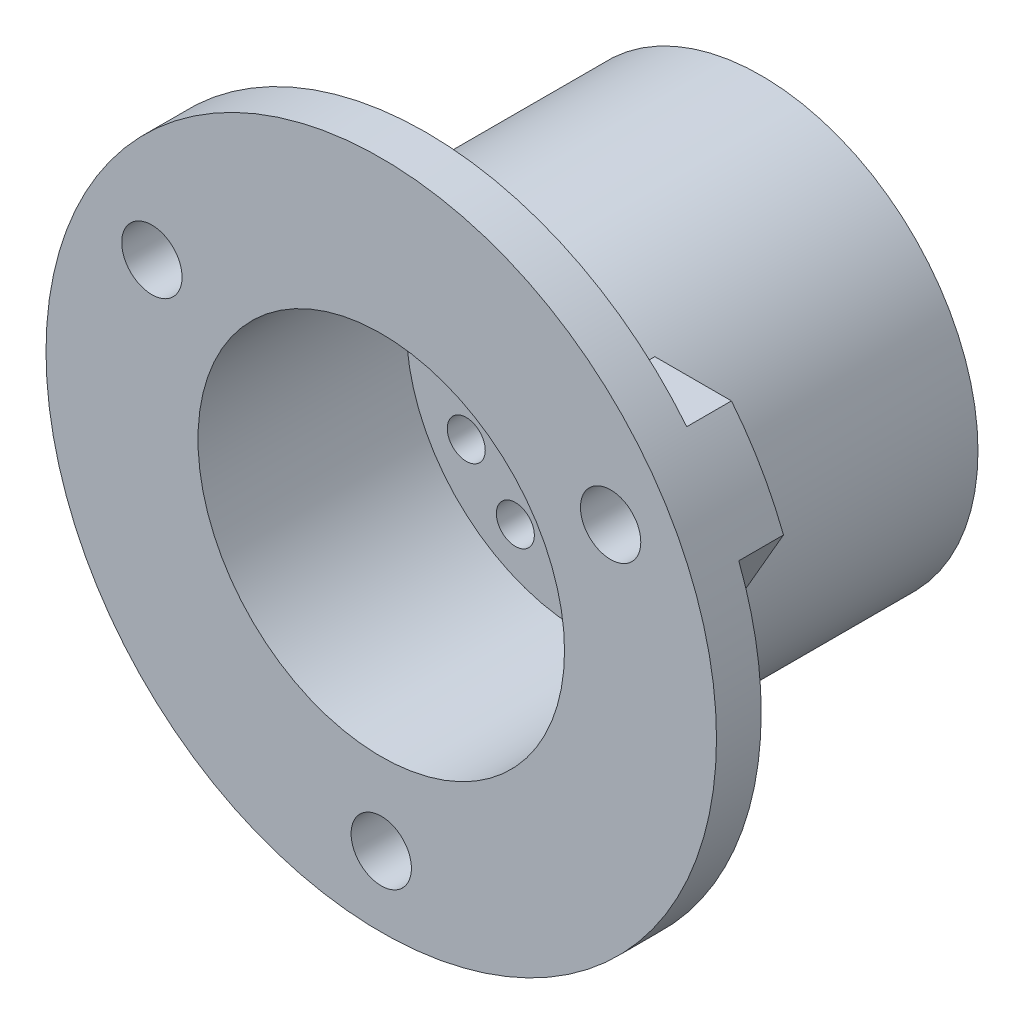
SolidWorks part; units mm, degrees
other "Spi connector"
ref_plane "Front Plane" through (0, 0, 0) normal (0, 0, 1) x (1, 0, 0)
ref_plane "Top Plane" through (0, 0, 0) normal (0, 1, 0) x (1, 0, 0)
ref_plane "Right Plane" through (0, 0, 0) normal (1, 0, 0) x (0, 0, -1)
sketch "Sketch1" plane through (0, 0, 0) normal (0, 0, 1) x (1, 0, 0)
  line L2 (1.75, -2.4) -> (-1.75, -2.4) construction
  circle A0 centre (0, 0) radius 7.875
  circle A1 centre (0, 6) radius 0.85
  circle A2 centre (3, 5.1962) radius 0.85
  circle A3 centre (5.1962, 3) radius 0.85
  circle A4 centre (6, 0) radius 0.85
  circle A5 centre (5.1962, -3) radius 0.85
  circle A6 centre (3, -5.1962) radius 0.85
  circle A7 centre (0, -6) radius 0.85 [skipped]
  circle A8 centre (-3, -5.1962) radius 0.85
  circle A9 centre (-5.1962, -3) radius 0.85
  circle A10 centre (-6, 0) radius 0.85
  circle A11 centre (-5.1962, 3) radius 0.85
  circle A12 centre (-3, 5.1962) radius 0.85
  circle A13 centre (1.75, -2.4) radius 0.85
  circle A14 centre (-1.75, -2.4) radius 0.85
  circle A15 centre (0, 1.6) radius 1.25
  point P30 (0, 0)
  point P34 (0, -2.4)
  dimension "D1" = 15.75
  dimension "D2" = 1.7
  dimension "D7" = 2.5
  dimension "D3" = 6
  dimension "D5" = 2.4
  dimension "D6" = 3.5
  dimension "D8" = 1.6
  dimension "D4" = 12
extrude "Boss-Extrude1" add sketch "Sketch1" along normal blind 5
sketch "Sketch2" plane through (0, 0, 0) normal (0, 0, 1) x (1, 0, 0)
  line L0 (0, -7.2) -> (0, -9.2) construction
  line L1 (1.5, -7.2) -> (1.5, -9.2)
  line L2 (-1.5, -7.2) -> (-1.5, -9.2)
  circle A0 centre (0, 0) radius 8.2
  arc A1 (1.5, -7.2) -> (-1.5, -7.2) centre (0, -7.2) ccw
  arc A2 (-1.5, -9.2) -> (1.5, -9.2) centre (0, -9.2) ccw
  circle A3 centre (0, 0) radius 12
  point P5 (0, -8.2)
  dimension "D1" = 16.4
  dimension "D2" = 1.5
  dimension "D4" = 24
  dimension "D3" = 1
sketch "Sketch3" [suppressed] plane through (0, 0, 0) normal (0, 0, 1) x (1, 0, 0)
  line L0 (-1.5, -7.2) -> (-1.5, -9.2) construction
  line L1 (-1.5, -8.0616) -> (-1.5, -9.2)
  line L2 (1.5, -7.2) -> (1.5, -9.2) construction
  line L3 (1.5, -8.0616) -> (1.5, -9.2)
  circle A0 centre (0, 0) radius 8.2 construction
  arc A1 (1.5, -8.0616) -> (-1.5, -8.0616) centre (0, 0) ccw
  arc A2 (-1.5, -9.2) -> (1.5, -9.2) centre (0, -9.2) ccw construction
  arc A3 (-1.5, -9.2) -> (1.5, -9.2) centre (0, -9.2) ccw
extrude "Extrude-Thin1" add sketch "Sketch2" along normal blind 14 and the other way blind 3 separate body thin contours A0 thin type one direction wall 1.5
sketch "Sketch4" plane through (0, 0, 14) normal (0, 0, 1) x (1, 0, 0)
  line L1 (2.3094, -11.85) -> (1.1547, -9.85)
  line L2 (1.1547, -9.85) -> (-1.1547, -9.85)
  line L3 (-1.1547, -9.85) -> (-2.3094, -11.85)
  line L4 (-2.3094, -11.85) -> (-1.1547, -13.85)
  line L5 (-1.1547, -13.85) -> (1.1547, -13.85)
  line L6 (1.1547, -13.85) -> (2.3094, -11.85)
  line L7 (4.0415, -11.85) -> (2.0207, -8.35)
  line L8 (2.0207, -8.35) -> (-2.0207, -8.35)
  line L9 (-2.0207, -8.35) -> (-4.0415, -11.85)
  line L10 (-4.0415, -11.85) -> (-2.0207, -15.35)
  line L11 (-2.0207, -15.35) -> (2.0207, -15.35)
  line L12 (2.0207, -15.35) -> (4.0415, -11.85)
  circle A0 centre (0, 0) radius 9.7 construction
  circle A1 centre (0, 0) radius 9.7
  circle A2 centre (0, 0) radius 15
  circle A3 centre (0, -11.85) radius 1.35
  circle A5 centre (0, -11.85) radius 2 construction
  circle A6 centre (0, -11.85) radius 3.5 construction
  circle A7 centre (-10.2624, 5.925) radius 1.35
  circle A8 centre (10.2624, 5.925) radius 1.35
  point P26 (0, 0)
  circle M1 centre (0, 0) radius 9.7
  dimension "D1" = 30
  dimension "D2" = 2.7
  dimension "D3" = 4
  dimension "D5" = 0.15
  dimension "D4" = 1.5
  dimension "D6" = 3
extrude "Boss-Extrude2" add sketch "Sketch4" against normal blind 2 contours A2 | A1 | A3
extrude "Boss-Extrude3" add sketch "Sketch4<4>" against normal blind 2 from surface contours L7 A2 L9 L10 L12 L6 L5 L4 L3 L2 L1 M1 region at (3.0992, -13.2848, 14) starting at face at (1.35, -11.85, 12)
sketch "Sketch4<4>" plane through (0, 0, 14) normal (0, 0, 1) x (1, 0, 0) same geometry as "Sketch4"
pattern_circular "CirPattern1" count 3 over 360 about axis through (0, 0, -3) along (0, 0, 1) of "Boss-Extrude3", "Boss-Extrude2"
extrude "Cut-Extrude1" cut sketch "Sketch4<5>" against normal blind 2 contours A7 | A8 | A3 region at (0, -11.85, 14) region at (-10.2624, 5.925, 14) region at (10.2624, 5.925, 14)
sketch "Sketch4<5>" plane through (0, 0, 14) normal (0, 0, 1) x (1, 0, 0) same geometry as "Sketch4"
